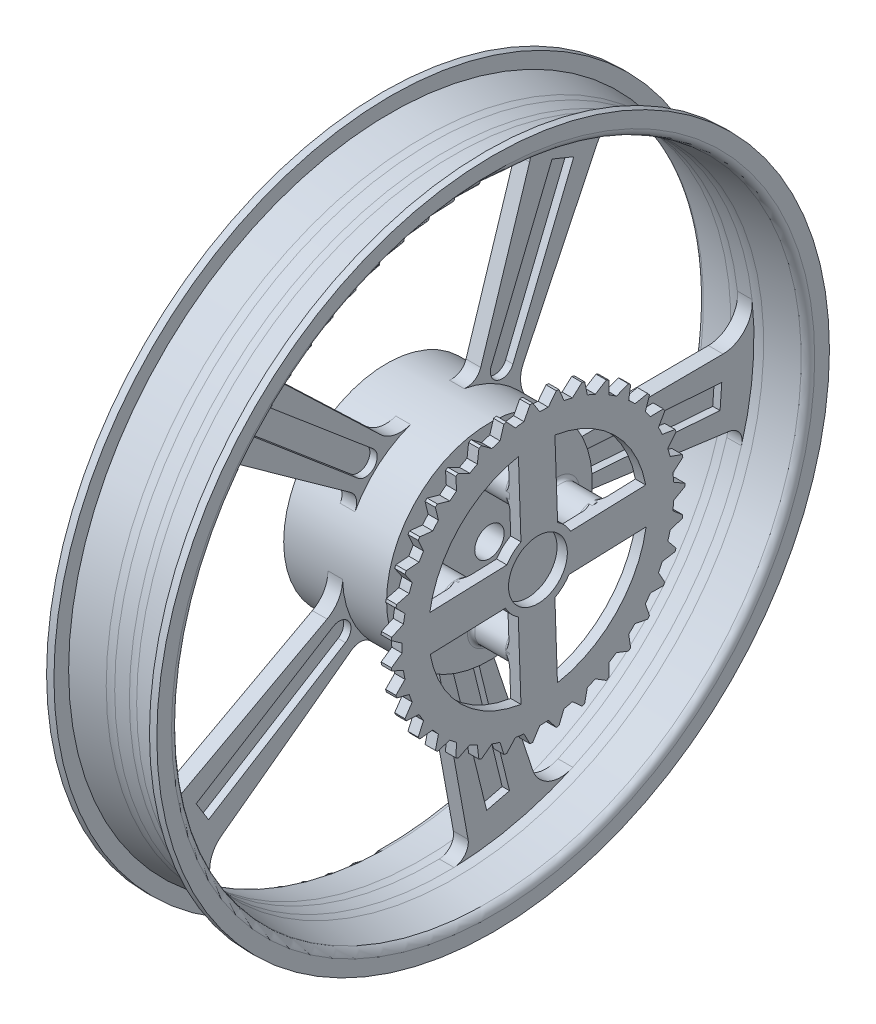
SolidWorks part; units mm, degrees
ref_plane "Front Plane" through (0, 0, 0) normal (0, 0, 1) x (1, 0, 0)
ref_plane "Top Plane" through (0, 0, 0) normal (0, 1, 0) x (1, 0, 0)
ref_plane "Right Plane" through (0, 0, 0) normal (1, 0, 0) x (0, 0, -1)
sketch "Sketch3" plane through (0, 0, 0) normal (0, 0, 1) x (1, 0, 0)
  line L0 (-74.3796, 0) -> (75.2003, 0) construction
  line L1 (0, 0) -> (0, 277.8479) construction
  line L2 (0, 0) -> (0, 70) construction
  line L4 (-35, 0) -> (-35, 70)
  line L5 (-35, 70) -> (35, 70)
  line L6 (35, 0) -> (35, 70)
  line L7 (-32.5, 228.8393) -> (-32.5, 218.8393)
  line L8 (-37.5, 228.8393) -> (-37.5, 218.8393)
  line L9 (0, 210) -> (-5, 210)
  line L10 (-11.1176, 210.4706) -> (-33.2647, 213.8981)
  line L11 (11.1176, 210.4706) -> (33.2647, 213.8981)
  line L12 (37.5, 228.8393) -> (37.5, 218.8393)
  line L13 (-10.3529, 215.4118) -> (-32.5, 218.8393)
  line L14 (0, 215) -> (-5, 215)
  line L15 (10.3529, 215.4118) -> (32.5, 218.8393)
  line L16 (32.5, 228.8393) -> (32.5, 218.8393)
  line L17 (-32.5, 228.8393) -> (-37.5, 228.8393)
  line L18 (32.5, 228.8393) -> (37.5, 228.8393)
  line L19 (-35, 0) -> (35, 0)
  line L20 (0, 215) -> (5, 215)
  line L21 (5, 210) -> (0, 210)
  arc A0 (-33.2647, 213.8981) -> (-37.5, 218.8393) centre (-32.5, 218.8393) cw
  arc A1 (-11.1176, 210.4706) -> (-5, 210) centre (-5, 250) ccw
  arc A2 (11.1176, 210.4706) -> (5, 210) centre (5, 250) cw
  arc A3 (33.2647, 213.8981) -> (37.5, 218.8393) centre (32.5, 218.8393) ccw
  arc A4 (-32.5, 218.8393) -> (-32.5, 218.8393) centre (-32.5, 218.8393) cw
  arc A5 (-10.3529, 215.4118) -> (-5, 215) centre (-5, 250) ccw
  arc A6 (10.3529, 215.4118) -> (5, 215) centre (5, 250) cw
  arc A7 (32.5, 218.8393) -> (32.5, 218.8393) centre (32.5, 218.8393) ccw
  point P5 (0, 210)
  point P7 (-37.5, 208.8393)
  point P12 (0, 230)
  point P20 (-37.5, 214.5536)
  point P23 (-8.0769, 210)
  point P27 (8.0769, 210)
  dimension "D8" = 5
  dimension "D1" = 210
  dimension "D2" = 70
  dimension "D3" = 70
  dimension "D4" = 75
  dimension "D5" = 10
  dimension "D6" = 230
  dimension "D7" = 5
  dimension "D9" = 10
revolve "Revolve2" add sketch "Sketch3" angle 360 about L0
sketch "Sketch4" plane through (0, 0, 0) normal (1, 0, 0) x (0, 0, -1)
  line L0 (21.238, 66.7004) -> (63.7139, 200.1013)
  line L1 (47.2856, 51.6146) -> (108.8728, 179.5737)
  arc A0 (47.2856, 51.6146) -> (21.238, 66.7004) centre (0, 0) ccw
  arc A1 (108.8728, 179.5737) -> (63.7139, 200.1013) centre (0, 0) ccw
extrude "Boss-Extrude1" add sketch "Sketch4" along normal mid plane 10
fillet "Fillet3" radius 10 2 edges at (0, 66.7004, -21.238) (0, 179.5737, -108.8728)
fillet "Fillet4" radius 20 2 edges at (0, 51.6146, -47.2856) (0, 200.1013, -63.7139)
sketch "Sketch5" plane through (0, 0, 0) normal (1, 0, 0) x (0, 0, -1)
  line L0 (24.0816, 75.6312) -> (31.203, 72.7256) construction
  line L1 (38.6102, 69.7035) -> (103.606, 229.0058) construction
  line L3 (46.0174, 66.6813) -> (87.4083, 168.129)
  line L5 (31.203, 72.7256) -> (72.5939, 174.1733)
  line L6 (72.5939, 174.1733) -> (87.4083, 168.129)
  line L7 (46.0174, 66.6813) -> (53.1388, 63.7758) construction
  arc A0 (31.203, 72.7256) -> (46.0174, 66.6813) centre (38.6102, 69.7035) ccw
  point P10 (80.0011, 171.1512)
  dimension "D1" = 8
extrude "Cut-Extrude1" cut sketch "Sketch5" along normal blind 10
pattern_circular "CirPattern1" count 5 over 360 about axis through (0, 0, 0) along (1, 0, 0) of "Boss-Extrude1", "Fillet3", "Fillet4", "Cut-Extrude1"
ref_plane "Plane1" through (-45, 0, 0) normal (-1, 0, 0) x (0, 0, 1)
sketch "Sketch7" plane through (-45, 0, 0) normal (-1, 0, 0) x (0, 0, 1)
  circle A0 centre (0, 0) radius 63.8312
  circle A1 centre (0, 0) radius 15
  dimension "D1" = 30
extrude "Cut-Extrude2" cut sketch "Sketch7" against normal blind 30
ref_plane "Plane2" through (0, 0, 0) normal (1, 0, 0) x (0, 0, -1)
sketch "Sketch8" plane through (0, 0, 0) normal (1, 0, 0) x (0, 0, -1)
  circle A0 centre (0, 0) radius 10
  dimension "D1" = 20
extrude "Cut-Extrude3" cut sketch "Sketch8" against normal mid plane 160
ref_plane "Plane3" through (35, 0, 0) normal (1, 0, 0) x (0, 0, -1)
sketch "Sketch9" plane through (35, 0, 0) normal (1, 0, 0) x (0, 0, -1)
  line L0 (0, 0) -> (0, 76.5621) construction
  circle A0 centre (0, 46.307) radius 12.5
  dimension "D1" = 25
extrude "Boss-Extrude2" add sketch "Sketch9" along normal blind 26
pattern_circular "CirPattern2" count 4 over 360 about axis through (0, 0, 0) along (1, 0, 0) of "Boss-Extrude2"
ref_plane "Plane4" through (61, 0, 0) normal (1, 0, 0) x (0, 0, -1)
sketch "Sketch10" plane through (61, 0, 0) normal (1, 0, 0) x (0, 0, -1)
  line L0 (3.9052, -116.3181) -> (-3.9052, 116.3181) construction
  line L1 (-13.2673, 73.3091) -> (-11.5505, 22.1718)
  line L2 (13.3763, 21.1205) -> (11.5505, 73.5992)
  line L3 (21.1205, -13.3763) -> (73.5992, -11.5505)
  line L4 (73.3091, 13.2673) -> (22.1718, 11.5505)
  line L5 (-13.3763, -21.1205) -> (-11.5505, -73.5992)
  line L6 (13.2673, -73.3091) -> (11.5505, -22.1718)
  line L7 (-21.1205, 13.3763) -> (-73.5992, 11.5505)
  line L8 (-73.3091, -13.2673) -> (-22.1718, -11.5505)
  circle A0 centre (0, 0) radius 92.5
  arc A1 (-13.2673, 73.3091) -> (-73.5992, 11.5505) centre (0, 0) ccw
  circle A2 centre (0, 0) radius 20
  circle A3 centre (0, 0) radius 25
  arc A4 (-73.3091, -13.2673) -> (-11.5505, -73.5992) centre (0, 0) ccw
  arc A5 (73.3091, 13.2673) -> (11.5505, 73.5992) centre (0, 0) ccw
  arc A6 (13.2673, -73.3091) -> (73.5992, -11.5505) centre (0, 0) ccw
  point P9 (0, 0)
  point P14 (12.4634, 47.3598)
  point P27 (0, 0)
  point P34 (0, 0)
  dimension "D1" = 185
  dimension "D2" = 18
  dimension "D3" = 40
  dimension "D4" = 5
  dimension "D8" = 185
  dimension "D5" = 10.8
  dimension "D7" = 4
  dimension "D6" = 4
extrude "Boss-Extrude4" add sketch "Sketch10" along normal blind 7
fillet "Fillet5" radius 2.5 8 edges at (35, 0, -33.807) (61, -0.3123, -58.8031) (35, -46.307, 12.5) (61, -58.8031, 0.3123) (35, 0, 58.807) (61, 0.3123, 58.8031) (35, 46.307, 12.5) (61, 58.8031, -0.3123)
ref_plane "Plane5" through (68, 0, 0) normal (1, 0, 0) x (0, 0, -1)
sketch "Sketch11" plane through (68, 0, 0) normal (1, 0, 0) x (0, 0, -1)
  line L0 (0, 0) -> (99.9929, 0) construction
  line L1 (99.9929, 0.9519) -> (99.9929, -0.9519)
  line L2 (99.9929, 0.9519) -> (87.9292, 7.9169)
  line L3 (87.9292, 7.9169) -> (87.9292, -7.9169)
  line L4 (87.9292, -7.9169) -> (99.9929, -0.9519)
  circle A0 centre (92.5, 0) radius 4.5708 construction
  circle A1 centre (0, 0) radius 92.5 construction
extrude "Boss-Extrude5" add sketch "Sketch11" against normal blind 7
pattern_circular "CirPattern3" count 35 over 360 about axis through (0, 0, 0) along (1, 0, 0) of "Boss-Extrude5"
